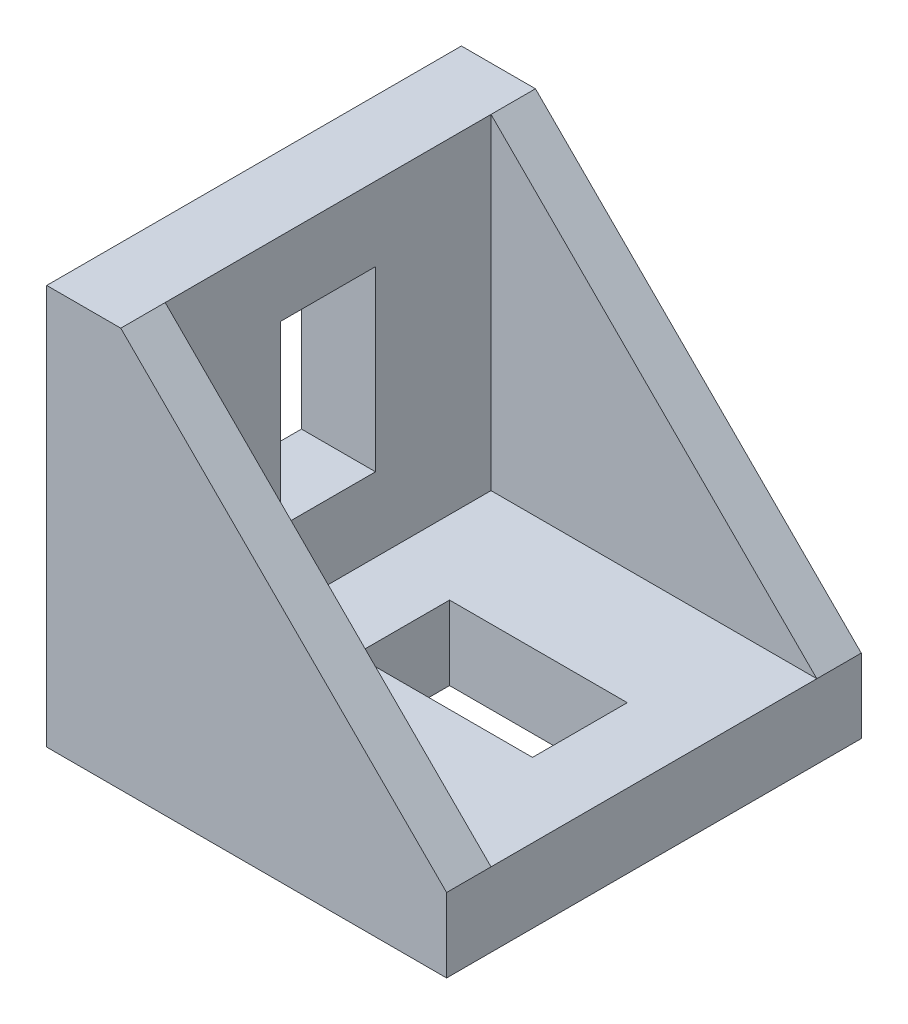
SolidWorks part; units mm, degrees
ref_plane "Front Plane" through (0, 0, 0) normal (0, 0, 1) x (1, 0, 0)
ref_plane "Top Plane" through (0, 0, 0) normal (0, 1, 0) x (1, 0, 0)
ref_plane "Right Plane" through (0, 0, 0) normal (1, 0, 0) x (0, 0, -1)
sketch "Sketch1" plane through (0, 0, 0) normal (0, 0, 1) x (1, 0, 0)
  line L0 (5, 27) -> (27, 5)
  line L1 (0, 0) -> (27, 0)
  line L2 (0, 0) -> (0, 27)
  line L3 (0, 27) -> (5, 27)
  line L4 (27, 0) -> (27, 5)
  line L5 (5, 27) -> (5, 5)
  line L6 (5, 5) -> (27, 5)
  dimension "D1" = 27
  dimension "D2" = 27
  dimension "D3" = 45
  dimension "D4" = 5
extrude "Boss-Extrude1" add sketch "Sketch1" along normal blind 28 contours L6 L5 L3 L2 L1 L4 region at (4.6182, 16, 0)
extrude "Boss-Extrude2" add sketch "Sketch1<3>" along normal blind 3 contours L5 L6 L0 region at (12.3333, 12.3333, 0)
sketch "Sketch1<3>" plane through (0, 0, 0) normal (0, 0, 1) x (1, 0, 0) same geometry as "Sketch1"
sketch "Sketch3" plane through (0, 0, 28) normal (0, 0, 1) x (1, 0, 0)
  line L0 (5, 27) -> (27, 5)
  line L1 (27, 5) -> (5, 5)
  line L2 (5, 5) -> (5, 27)
extrude "Boss-Extrude3" add sketch "Sketch3" against normal blind 3
sketch "Sketch4" plane through (5, 0, 0) normal (1, 0, 0) x (0, 0, -1)
  line L0 (-25, 27) -> (-3, 27) construction
  line L1 (-17.2, 10) -> (-10.8, 10)
  line L2 (-17.2, 10) -> (-17.2, 22)
  line L3 (-17.2, 22) -> (-10.8, 22)
  line L4 (-10.8, 10) -> (-10.8, 22)
  line L5 (-17.2, 10) -> (-10.8, 22) construction
  line L6 (-17.2, 22) -> (-10.8, 10) construction
  line L7 (0, 27) -> (0, 5) construction
  point P0 (-14, 16)
  dimension "D1" = 6.4
  dimension "D2" = 12
  dimension "D3" = 11
  dimension "D4" = 14
extrude "Cut-Extrude1" cut sketch "Sketch4" against normal blind 5
sketch "Sketch5" plane through (0, 5, 0) normal (0, 1, 0) x (1, 0, 0)
  line L0 (5, 0) -> (27, 0) construction
  line L1 (22, -17.2) -> (10, -17.2)
  line L2 (22, -17.2) -> (22, -10.8)
  line L3 (22, -10.8) -> (10, -10.8)
  line L4 (10, -17.2) -> (10, -10.8)
  line L5 (22, -17.2) -> (10, -10.8) construction
  line L6 (22, -10.8) -> (10, -17.2) construction
  line L7 (27, -25) -> (27, -3) construction
  point P0 (16, -14)
  dimension "D1" = 6.4
  dimension "D2" = 12
  dimension "D3" = 14
  dimension "D4" = 11
extrude "Cut-Extrude2" cut sketch "Sketch5" against normal blind 5
